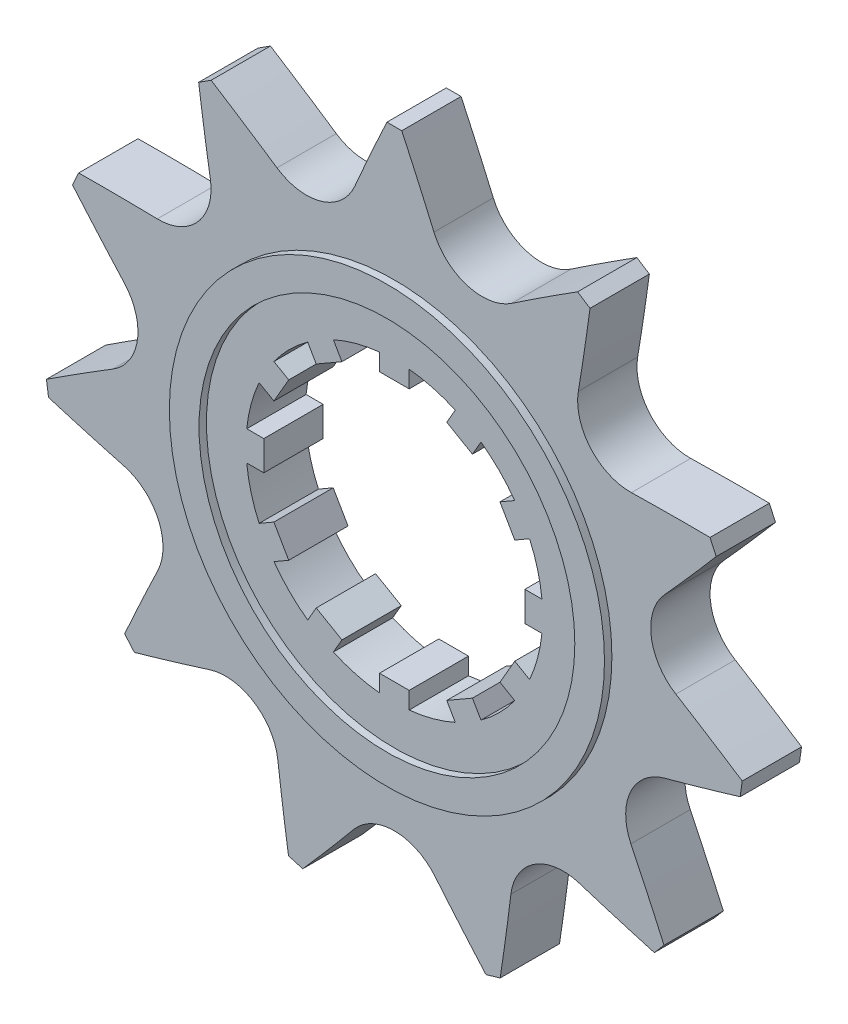
SolidWorks part; units mm, degrees
material "7075-T6 (SN)"
ref_plane "Front Plane" through (0, 0, 0) normal (0, 0, 1) x (1, 0, 0)
ref_plane "Top Plane" through (0, 0, 0) normal (0, 1, 0) x (1, 0, 0)
ref_plane "Right Plane" through (0, 0, 0) normal (1, 0, 0) x (0, 0, -1)
sketch "Sketch1" plane through (0, 0, 0) normal (0, 0, 1) x (1, 0, 0)
  line L1 (12.1856, -18.9611) -> (20.5023, -9.3631)
  line L2 (20.5023, -9.3631) -> (22.3097, 3.2076)
  line L3 (22.3097, 3.2076) -> (17.0339, 14.76)
  line L4 (17.0339, 14.76) -> (6.35, 21.6261)
  line L5 (6.35, 21.6261) -> (-6.35, 21.6261)
  line L6 (-6.35, 21.6261) -> (-17.0339, 14.76)
  line L7 (-17.0339, 14.76) -> (-22.3097, 3.2076)
  line L8 (-22.3097, 3.2076) -> (-20.5023, -9.3631)
  line L9 (-20.5023, -9.3631) -> (-12.1856, -18.9611)
  line L10 (-12.1856, -18.9611) -> (0, -22.5391)
  line L11 (0, -22.5391) -> (12.1856, -18.9611)
  circle A0 centre (0, 0) radius 21.6261 construction
  circle A1 centre (0, 0) radius 17.5 construction
  point P1 (0, 21.6261)
  dimension "D2" = 35
  dimension "D1" = 12.7
sketch "Sketch2" plane through (0, 0, 0) normal (0, 0, 1) x (1, 0, 0)
  line L0 (0, 0) -> (0, 21.6261) construction
  line L1 (6.35, 21.6261) -> (-6.35, 21.6261) construction
  line L2 (0, 21.6261) -> (0, 23.6261) construction
  line L3 (-1.5, 23.6261) -> (1.5, 23.6261) construction
  line L4 (0, 0) -> (-6.35, 21.6261) construction
  line L5 (0, 0) -> (6.35, 21.6261) construction
  line L6 (-1.5, 23.6261) -> (-3.0486, 17.2324) construction
  line L7 (1.5, 23.6261) -> (3.0486, 17.2324) construction
  line L8 (-0.5, 23.6261) -> (0.5, 23.6261)
  circle A0 centre (0, 0) radius 17.5 construction
  arc A1 (-4.9303, 16.7911) -> (-2.6711, 18.7911) centre (-5.9303, 20.1968) ccw
  arc A2 (-2.6711, 18.7911) -> (-0.5, 23.6261) centre (161.1314, -51.8562) cw
  arc A3 (4.9303, 16.7911) -> (2.6711, 18.7911) centre (5.9303, 20.1968) cw
  arc A4 (2.6711, 18.7911) -> (0.5, 23.6261) centre (-161.1314, -51.8562) ccw
  arc A6 (-4.9303, 16.7911) -> (4.9303, 16.7911) centre (0, 0) cw
  point P8 (0, 23.6261)
  dimension "D1" = 2
  dimension "D2" = 3
  dimension "D3" = 6.0972
  dimension "D4" = 2
  dimension "D5" = 0.5
extrude "Boss-Extrude1" add sketch "Sketch2" along normal blind 2 and the other way blind 2
sketch "Sketch3" plane through (0, 0, 0) normal (1, 0, 0) x (0, 0, -1)
  line L0 (2, 23.6261) -> (-2, 23.6261) construction
  line L1 (0, 0) -> (0, 32.0556) construction
  line L2 (-0.5, 23.6261) -> (0.5, 23.6261)
  line L3 (2, 18.7911) -> (6.2612, 18.7911)
  line L4 (6.2612, 18.7911) -> (6.2612, 31.1396)
  line L5 (6.2612, 31.1396) -> (-6.4823, 31.1396)
  line L6 (-6.4823, 31.1396) -> (-6.4823, 18.7911)
  line L7 (-6.4823, 18.7911) -> (-2, 18.7911)
  arc A0 (-2, 18.7911) -> (-0.5, 23.6261) centre (22.5046, 13.839) cw
  arc A1 (2, 18.7911) -> (0.5, 23.6261) centre (-22.5046, 13.839) ccw
  dimension "D2" = 25
  dimension "D1" = 0.5
sketch3d "3DSketch1"
  line L0 (0, 0, 0) -> (0, 0, -4.5404) construction
pattern_circular "CirPattern1" count 11 over 360 about axis through (0, 0, 0) along (0, 0, -1) of "Boss-Extrude1"
sketch "Sketch4" plane through (0, 0, 0) normal (0, 0, 1) x (1, 0, 0)
  circle A0 centre (0, 0) radius 17.5 construction
  circle A1 centre (0, 0) radius 17.5
extrude "Boss-Extrude2" add sketch "Sketch4" along normal blind 2 and the other way blind 2
sketch "Sketch6" plane through (0, 0, 2) normal (0, 0, 1) x (1, 0, 0)
  circle A0 centre (0, 0) radius 14.669
  circle A1 centre (0, 0) radius 12.669
  dimension "D1" = 29.338
  dimension "D2" = 2
extrude "Boss-Extrude4" add sketch "Sketch6" along normal blind 0.5
sketch "Sketch7" plane through (0, 0, 2) normal (0, 0, 1) x (1, 0, 0)
  circle A1 centre (0, 0) radius 10
  dimension "D1" = 20
extrude "Cut-Extrude1" cut sketch "Sketch7" against normal up to surface (4 mm away) up to face at (0, 0, -2)
sketch "Sketch8" plane through (0, 0, 2) normal (0, 0, 1) x (1, 0, 0)
  line L0 (0, 0) -> (0, 10) construction
  line L1 (1, 10) -> (-1, 10)
  line L2 (-1, 10) -> (-1, 8.8)
  line L3 (-1, 8.8) -> (1, 8.8)
  line L4 (1, 10) -> (1, 8.8)
  circle A0 centre (0, 0) radius 10 construction
  point P10 (0, 8.8)
  dimension "D1" = 1.2
  dimension "D2" = 2
extrude "Boss-Extrude5" add sketch "Sketch8" against normal up to surface (4 mm away) up to face at (-10, 0, -2)
pattern_circular "CirPattern2" count 12 over 360 about axis through (0, 0, 2.5) along (0, 0, -1) of "Boss-Extrude5"
